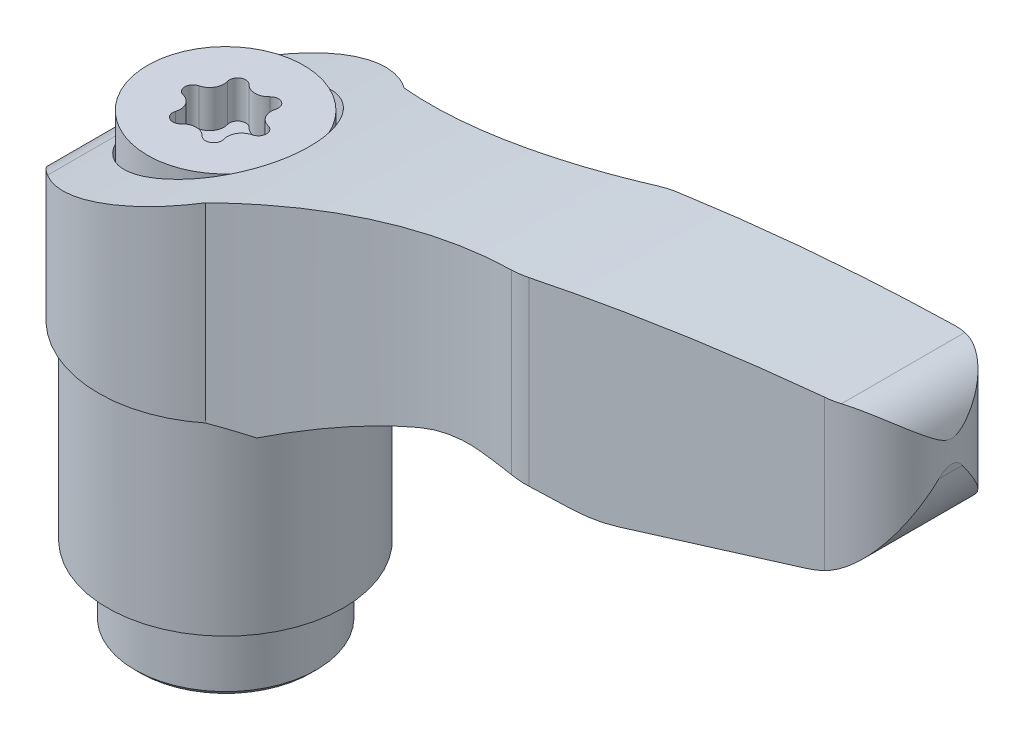
SolidWorks part; units mm, degrees
ref_plane "Front Plane" through (0, 0, 0) normal (0, 0, 1) x (1, 0, 0)
ref_plane "Top Plane" through (0, 0, 0) normal (0, 1, 0) x (1, 0, 0)
ref_plane "Right Plane" through (0, 0, 0) normal (1, 0, 0) x (0, 0, -1)
ref_plane "Plane4" through (0, 0, 0) normal (0, 0, 1) x (1, 0, 0)
sketch "Sketch1" plane through (0, 0, 0) normal (0, 0, 1) x (1, 0, 0)
  line L0 (-6.51, 14.5) -> (6.49, 14.5)
  line L1 (17.7504, 19) -> (23.0467, 19)
  line L2 (25.5108, 19.3419) -> (35.5345, 22.1783)
  line L3 (39.939, 27.2042) -> (40.039, 27.8935)
  line L4 (-6.51, 18.7873) -> (-6.51, 14.5)
  arc A0 (6.49, 14.5) -> (14.256, 18.2982) centre (42.8289, -49.963) cw
  arc A1 (14.256, 18.2982) -> (17.7504, 19) centre (17.7504, 9.95) cw
  arc A2 (23.0467, 19) -> (25.5108, 19.3419) centre (23.0467, 28.05) ccw
  arc A3 (35.5345, 22.1783) -> (39.939, 27.2042) centre (33.8627, 28.0864) ccw
  arc A4 (40.039, 27.8935) -> (37.324, 30.8632) centre (37.466, 28.267) ccw
  arc A5 (37.324, 30.8632) -> (-4.2518, 22.0596) centre (44.8872, -107.4302) ccw
  arc A6 (-4.2518, 22.0596) -> (-6.51, 18.7873) centre (-3.01, 18.7873) ccw
  dimension "D1" = 74
  dimension "D2" = 9.05
  dimension "D3" = 6.14
  dimension "D4" = 2.6
  dimension "D5" = 138.5
  dimension "D6" = 3.5
  dimension "D7" = 6.49
  dimension "D8" = 14.256
  dimension "D9" = 17.7504
  dimension "D10" = 23.0467
  dimension "D11" = 25.5108
  dimension "D12" = 33.8627
  dimension "D13" = 37.324
  dimension "D14" = 37.466
  dimension "D15" = 39.939
  dimension "D16" = 3.01
  dimension "D17" = 9.95
extrude "Extrude1" add sketch "Sketch1" against normal blind 8 and the other way blind 8
ref_plane "Plane5" through (0, 0, 0) normal (0, 0, 1) x (1, 0, 0)
sketch "Sketch2" plane through (0, 0, 0) normal (0, 0, 1) x (1, 0, 0)
  line L0 (-0.01, 4) -> (-6.51, 4)
  line L1 (-6.51, 4) -> (-6.51, 16.5625)
  line L2 (-6.51, 16.5625) -> (-0.01, 16.5625)
  line L3 (-0.01, 16.5625) -> (-0.01, 4)
  line L4 (-0.01, 16.5625) -> (-0.01, 4) construction
  dimension "D1" = 0.01
  dimension "D2" = 6.51
  dimension "D3" = 4
  dimension "D4" = 16.5625
revolve "Revolve1" add sketch "Sketch2" angle 360 about L4 reverse direction yes
ref_plane "Plane6" through (0, 31, 0) normal (0, 1, 0) x (-1, 0, 0)
sketch "Sketch3" plane through (0, 31, 0) normal (0, 1, 0) x (-1, 0, 0)
  line L0 (40, 40) -> (-54, 40)
  line L1 (-54, 40) -> (-54, -54)
  line L2 (-54, -54) -> (40, -54)
  line L3 (40, -54) -> (40, 40)
  line L4 (-20.791, 4.0815) -> (-36.5, 3.5)
  line L5 (-36.5, -3.5) -> (-20.791, -4.0815)
  arc A0 (-4.3628, -5.4741) -> (-4.3628, 5.4741) centre (0, 0) ccw
  arc A1 (-4.3628, 5.4741) -> (-19.7766, 4.0157) centre (-14.8, 33.6) cw
  arc A2 (-19.7766, 4.0157) -> (-20.791, 4.0815) centre (-20.6061, -0.9151) ccw
  arc A3 (-36.5, 3.5) -> (-36.5, -3.5) centre (-36.5, 0) ccw
  arc A4 (-20.791, -4.0815) -> (-19.7766, -4.0157) centre (-20.6061, 0.9151) ccw
  arc A5 (-19.7766, -4.0157) -> (-4.3628, -5.4741) centre (-14.8, -33.6) cw
  dimension "D1" = 7
  dimension "D2" = 30
  dimension "D3" = 5
  dimension "D4" = 3.5
  dimension "D5" = 40
  dimension "D6" = 4.3628
  dimension "D7" = 14.8
  dimension "D8" = 19.7766
  dimension "D9" = 20.791
  dimension "D10" = 54
  dimension "D11" = 40
extrude "Extrude2" cut sketch "Sketch3" against normal blind 31
ref_plane "Plane7" through (0, 0, 0) normal (0, 0, 1) x (1, 0, 0)
sketch "Sketch4" plane through (0, 0, 0) normal (0, 0, 1) x (1, 0, 0)
  line L0 (-40, 0) -> (54, 0)
  line L1 (54, 0) -> (54, 47)
  line L2 (54, 47) -> (-40, 47)
  line L3 (-40, 47) -> (-40, 0)
  line L4 (-6.51, 18.7873) -> (-6.51, 4.15)
  line L5 (-6.51, 4.15) -> (-6.36, 4)
  line L6 (-6.36, 4) -> (6.49, 4)
  line L7 (6.49, 4) -> (6.49, 9.6432)
  line L8 (17.7504, 19) -> (23.0467, 19)
  line L9 (25.5108, 19.3419) -> (35.5345, 22.1783)
  line L10 (39.939, 27.2042) -> (40.039, 27.8935)
  arc A0 (6.49, 9.6432) -> (11.055, 16.8682) centre (14.49, 9.6432) cw
  arc A1 (11.055, 16.8682) -> (14.256, 18.2982) centre (42.8289, -49.963) cw
  arc A2 (14.256, 18.2982) -> (17.7504, 19) centre (17.7504, 9.95) cw
  arc A3 (23.0467, 19) -> (25.5108, 19.3419) centre (23.0467, 28.05) ccw
  arc A4 (35.5345, 22.1783) -> (39.939, 27.2042) centre (33.8627, 28.0864) ccw
  arc A5 (40.039, 27.8935) -> (37.324, 30.8632) centre (37.466, 28.267) ccw
  arc A6 (37.324, 30.8632) -> (-4.2518, 22.0596) centre (44.8872, -107.4302) ccw
  arc A7 (-4.2518, 22.0596) -> (-6.51, 18.7873) centre (-3.01, 18.7873) ccw
  dimension "D1" = 8
  dimension "D2" = 74
  dimension "D3" = 9.05
  dimension "D4" = 6.14
  dimension "D5" = 2.6
  dimension "D6" = 138.5
  dimension "D7" = 3.5
  dimension "D8" = 6.49
  dimension "D9" = 11.055
  dimension "D10" = 14.256
  dimension "D11" = 23.0467
  dimension "D12" = 25.5108
  dimension "D13" = 33.8627
  dimension "D14" = 37.324
  dimension "D15" = 37.466
  dimension "D16" = 39.939
  dimension "D17" = 3.01
  dimension "D18" = 4
  dimension "D19" = 4.15
  dimension "D20" = 9.6432
  dimension "D23" = 54
  dimension "D26" = 6.36
  dimension "D28" = 40
  dimension "D38" = 47
extrude "Extrude3" cut sketch "Sketch4" against normal blind 14 and the other way blind 14
ref_plane "Plane8" through (0, 0, 0) normal (0, 0, 1) x (1, 0, 0)
sketch "Sketch5" plane through (0, 0, 0) normal (0, 0, 1) x (1, 0, 0)
  line L0 (0, 28.5) -> (4.9264, 28.5)
  line L1 (4.9264, 28.5) -> (4.3, 21.34)
  line L2 (4.3, 21.34) -> (4.3, 16)
  line L3 (4.3, 16) -> (2.5, 16)
  line L4 (2.5, 16) -> (2.5, 15)
  line L5 (2.5, 15) -> (4.15, 15)
  line L6 (4.15, 15) -> (4.15, 12.8)
  line L7 (4.15, 12.8) -> (5, 12.8)
  line L8 (5, 12.8) -> (5, 4.55)
  line L9 (5, 4.55) -> (5.25, 4.3)
  line L10 (5.25, 4.3) -> (5.25, 3)
  line L11 (5.25, 3) -> (0, 3)
  line L12 (0, 3) -> (0, 28.5)
  line L13 (0, 4) -> (0, 28.5) construction
  dimension "D1" = 2.5
  dimension "D2" = 4.15
  dimension "D3" = 4.3
  dimension "D4" = 4.9264
  dimension "D5" = 5
  dimension "D6" = 5.25
  dimension "D7" = 3
  dimension "D8" = 4.3
  dimension "D9" = 4.55
  dimension "D10" = 12.8
  dimension "D11" = 15
  dimension "D12" = 16
  dimension "D13" = 21.34
  dimension "D14" = 28.5
revolve "Cut-Revolve1" cut sketch "Sketch5" angle 360 about L13 reverse direction yes
ref_plane "Plane9" through (0, 0, 0) normal (0, 0, 1) x (1, 0, 0)
sketch "Sketch6" plane through (0, 0, 0) normal (0, 0, 1) x (1, 0, 0)
  line L0 (0, 24.5) -> (4.3, 24.5)
  line L1 (4.3, 24.5) -> (4.3, 21.339)
  line L2 (4.3, 21.339) -> (2.5, 21.339)
  line L3 (2.5, 21.339) -> (2.5, 15)
  line L4 (2.5, 15) -> (4.15, 15)
  line L5 (4.15, 15) -> (4.15, 12.8)
  line L6 (4.15, 12.8) -> (5, 12.8)
  line L7 (5, 12.8) -> (5, 0.3)
  line L8 (5, 0.3) -> (4.7, 0)
  line L9 (4.7, 0) -> (0, 0)
  line L10 (0, 0) -> (0, 24.5)
  line L11 (0, 0) -> (0, 24.5) construction
  dimension "D1" = 2.5
  dimension "D2" = 4.15
  dimension "D3" = 4.3
  dimension "D4" = 4.7
  dimension "D5" = 5
  dimension "D6" = 0.3
  dimension "D7" = 12.8
  dimension "D8" = 15
  dimension "D9" = 21.339
  dimension "D10" = 24.5
revolve "Revolve2" add sketch "Sketch6" angle 360 about L11 reverse direction yes
ref_plane "Plane10" through (0, 24.5, 0) normal (0, 1, 0) x (-1, 0, 0)
sketch "Sketch7" plane through (0, 24.5, 0) normal (0, 1, 0) x (-1, 0, 0)
  arc A0 (1.9038, -0.4379) -> (1.9038, 0.4379) centre (1.8, 0) ccw
  arc A1 (1.9038, 0.4379) -> (1.3311, 1.4298) centre (2.0856, 1.2041) cw
  arc A2 (1.3311, 1.4298) -> (0.5727, 1.8677) centre (0.9, 1.5588) ccw
  arc A3 (0.5727, 1.8677) -> (-0.5727, 1.8677) centre (0, 2.4082) cw
  arc A4 (-0.5727, 1.8677) -> (-1.3311, 1.4298) centre (-0.9, 1.5588) ccw
  arc A5 (-1.3311, 1.4298) -> (-1.9038, 0.4379) centre (-2.0856, 1.2041) cw
  arc A6 (-1.9038, 0.4379) -> (-1.9038, -0.4379) centre (-1.8, 0) ccw
  arc A7 (-1.9038, -0.4379) -> (-1.3311, -1.4298) centre (-2.0856, -1.2041) cw
  arc A8 (-1.3311, -1.4298) -> (-0.5727, -1.8677) centre (-0.9, -1.5588) ccw
  arc A9 (-0.5727, -1.8677) -> (0.5727, -1.8677) centre (0, -2.4082) cw
  arc A10 (0.5727, -1.8677) -> (1.3311, -1.4298) centre (0.9, -1.5588) ccw
  arc A11 (1.3311, -1.4298) -> (1.9038, -0.4379) centre (2.0856, -1.2041) cw
  dimension "D1" = 0.45
  dimension "D2" = 0.7875
  dimension "D3" = 0.5727
  dimension "D4" = 1.3311
  dimension "D5" = 1.8
extrude "Extrude4" cut sketch "Sketch7" against normal blind 2.06 and the other way blind 2.06
ref_plane "Plane11" through (0, 0, 0) normal (0, 0, 1) x (1, 0, 0)
sketch "Sketch8" plane through (0, 0, 0) normal (0, 0, 1) x (1, 0, 0)
  line L0 (0, 12.4194) -> (2.4585, 11)
  line L1 (2.4585, 11) -> (2.4585, 0.5415)
  line L2 (2.4585, 0.5415) -> (3, 0)
  line L3 (3, 0) -> (0, 0)
  line L4 (0, 0) -> (0, 12.4194)
  line L5 (0, 0) -> (0, 12.4194) construction
  dimension "D1" = 2.4585
  dimension "D2" = 3
  dimension "D3" = 0.5415
  dimension "D4" = 11
  dimension "D5" = 12.4194
revolve "Cut-Revolve2" cut sketch "Sketch8" angle 360 about L5 reverse direction yes
cosmetic thread "Cosmetic Thread1" parameters "D1"=9, "D2"=6
